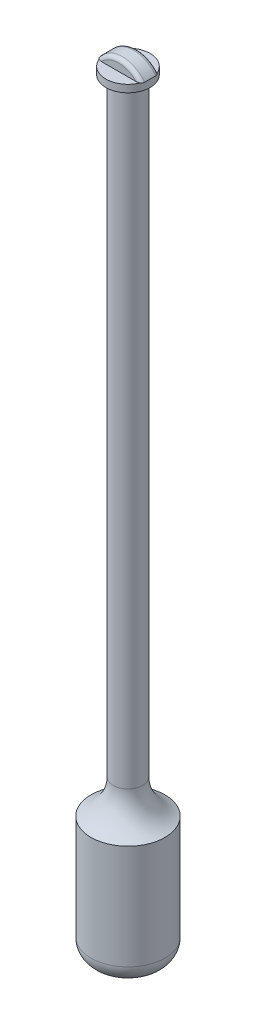
SolidWorks part; units mm, degrees
ref_plane "Front Plane" through (0, 0, 0) normal (0, 0, 1) x (1, 0, 0)
ref_plane "Top Plane" through (0, 0, 0) normal (0, 1, 0) x (1, 0, 0)
ref_plane "Right Plane" through (0, 0, 0) normal (1, 0, 0) x (0, 0, -1)
sketch "Sketch1" plane through (0, 0, 0) normal (0, 0, 1) x (1, 0, 0)
  line L0 (0, 0) -> (5, 0)
  line L1 (10, 5) -> (10, 33.2857)
  line L2 (3.989, 42.4556) -> (3.989, 207)
  line L3 (3.989, 207) -> (6, 207)
  line L4 (6, 207) -> (6, 209)
  line L5 (6, 209) -> (0, 209)
  line L6 (0, 0) -> (0, -136.1987) construction
  line L7 (0, 0) -> (0, 209)
  arc A0 (10, 33.2857) -> (3.989, 42.4556) centre (13.989, 42.4556) cw
  arc A1 (5, 0) -> (10, 5) centre (5, 5) ccw
  point P6 (3.989, 42.4556)
  point P13 (10, 0)
  dimension "D1" = 209
  dimension "D2" = 10
  dimension "D6" = 5
  dimension "D3" = 10
  dimension "D4" = 2
  dimension "D5" = 6
revolve "Revolve1" add sketch "Sketch1" angle 360 about L6
sketch "Sketch2" plane through (0, 0, 0) normal (0, 0, 1) x (1, 0, 0)
  line L0 (-6, 209) -> (6, 209)
  arc A0 (-6, 209) -> (6, 209) centre (0, 204.5) cw
  dimension "D1" = 7.5
extrude "Boss-Extrude1" add sketch "Sketch2" along normal mid plane 5
fillet "Fillet1" radius 1 2 edges at (0, 212, 2.5) (0, 212, -2.5)
